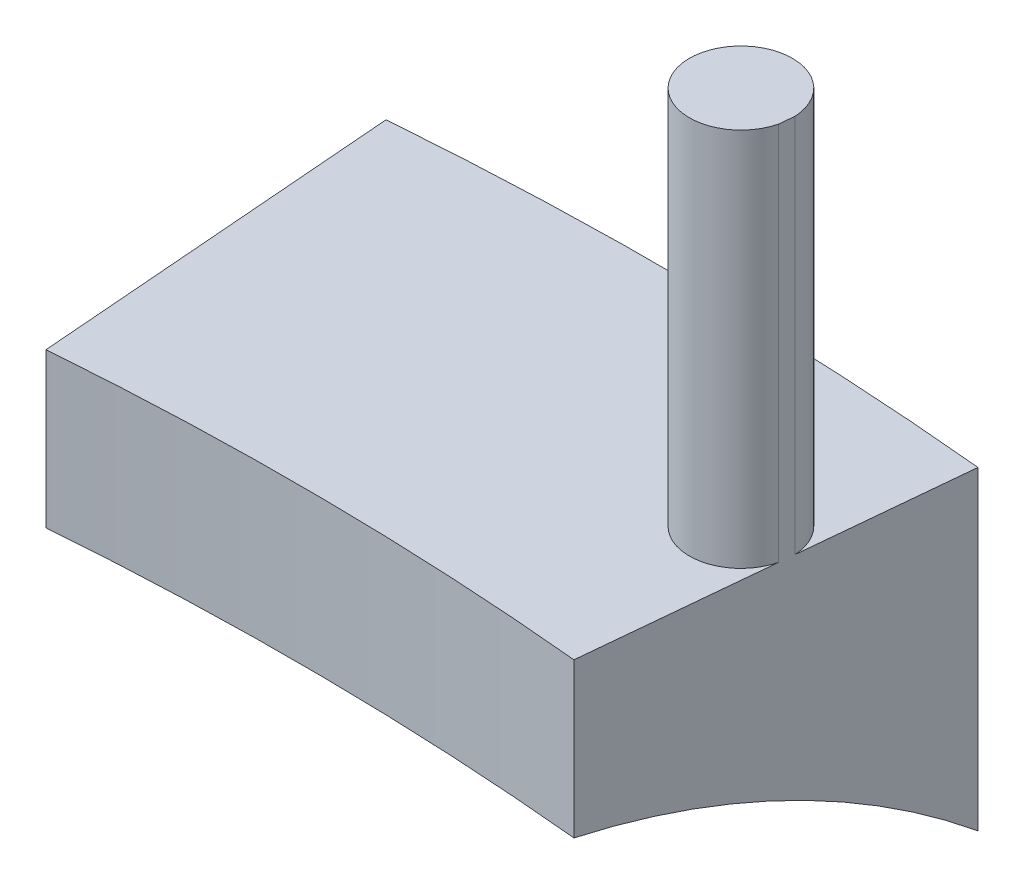
SolidWorks part; units mm, degrees
ref_plane "Front Plane" through (0, 0, 0) normal (0, 0, 1) x (1, 0, 0)
ref_plane "Top Plane" through (0, 0, 0) normal (0, 1, 0) x (1, 0, 0)
ref_plane "Right Plane" through (0, 0, 0) normal (1, 0, 0) x (0, 0, -1)
sketch "Sketch1" plane through (0, 0, 0) normal (0, 1, 0) x (1, 0, 0)
  circle A0 centre (0, 0) radius 140.97
  circle A1 centre (0, 0) radius 125.73
  dimension "D1" = 281.94
  dimension "D2" = 251.46
extrude "Boss-Extrude1" add sketch "Sketch1" along normal blind 12.954
sketch "Sketch3" plane through (0, 12.954, 0) normal (0, 1, 0) x (1, 0, 0)
  line L0 (0, 0) -> (13.4916, 140.3229)
  line L1 (13.4916, 140.3229) -> (0, 0)
  line L2 (0, 0) -> (-11.0802, 140.5339)
  circle A0 centre (0, 0) radius 140.97 construction
  circle A1 centre (0, 0) radius 140.97
  circle M3 centre (0, 0) radius 140.97
  circle M4 centre (0, 0) radius 125.73
  dimension "D1" = 10
extrude "Cut-Extrude1" cut sketch "Sketch3" against normal blind 12.954 contours L0 L2 M4 | L2 L0 M4 M3 region at (-0.0205, 12.954, 2.3917) region at (16.7282, 12.954, -132.3566)
sketch "Sketch5" plane through (0, 0, 0) normal (0, 1, 0) x (1, 0, 0)
  line L0 (-9.8823, 125.341) -> (-11.0802, 140.5339) construction
  line L1 (12.033, 125.1529) -> (13.4916, 140.3229) construction
  arc A1 (-10.4813, 132.9374) -> (12.7623, 132.7379) centre (0, 0) cw
  circle A2 centre (10.7123, 133.3451) radius 2.1209
  dimension "D1" = 4.2418
  dimension "D2" = 2.05
  dimension "D3" = 133.35
extrude "Boss-Extrude2" add sketch "Sketch5" along normal blind 28.575 contours A2
sketch "Sketch2" plane through (0, 0, 0) normal (0, 0, 1) x (1, 0, 0)
  line L0 (0, 12.954) -> (-125.73, 12.954)
  line L1 (13.4916, 12.954) -> (-11.0802, 12.954) construction
  line L2 (-125.73, 12.954) -> (-125.73, 6.604)
  line L3 (-125.73, 6.604) -> (-125.73, 0)
  line L4 (-125.73, 0) -> (-140.97, 0)
  line L5 (0, 0) -> (0, 30.8515)
  arc A0 (-125.73, 6.604) -> (-140.97, 0) centre (-121.1655, -24.8162) ccw
  dimension "D3" = 31.75
  dimension "D1" = 125.73
  dimension "D2" = 6.35
revolve "Cut-Revolve1" cut sketch "Sketch2" angle 360 about L5
sketch "Sketch6" plane through (0, 0, 0) normal (0.9954, 0, 0.0957) x (0.0957, 0, -0.9954)
  line L1 (114.9487, -1.4366) -> (150.8904, -1.4366)
  line L2 (114.9487, -1.4366) -> (114.9487, 48.5634)
  line L3 (114.9487, 48.5634) -> (150.8904, 48.5634)
  line L4 (150.8904, -1.4366) -> (150.8904, 48.5634)
  dimension "D1" = 50
extrude "Cut-Extrude2" cut sketch "Sketch6" along normal blind 25.4
